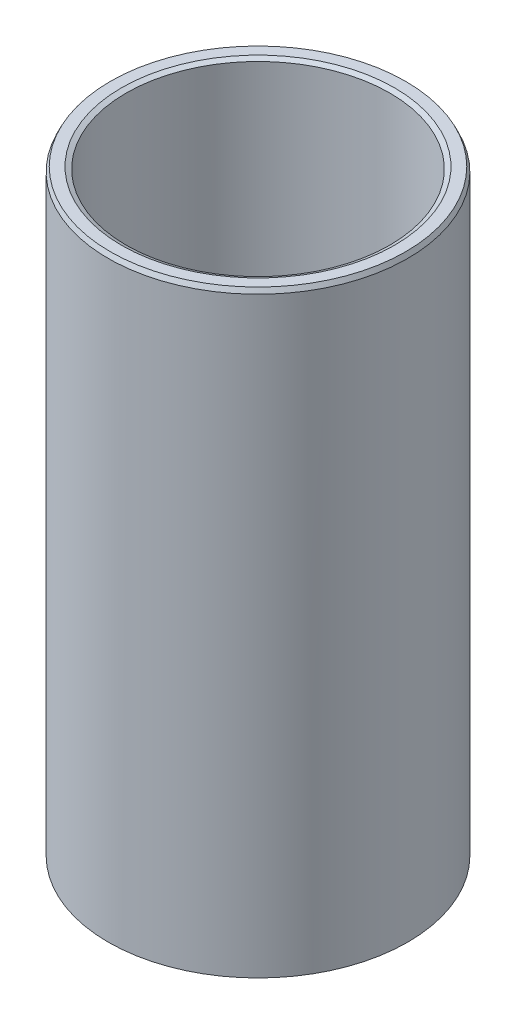
SolidWorks part; units mm, degrees
ref_plane "Front Plane" through (0, 0, 0) normal (0, 0, 1) x (1, 0, 0)
ref_plane "Top Plane" through (0, 0, 0) normal (0, 1, 0) x (1, 0, 0)
ref_plane "Right Plane" through (0, 0, 0) normal (1, 0, 0) x (0, 0, -1)
sketch "Sketch1" plane through (0, 0, 0) normal (0, 1, 0) x (1, 0, 0)
  circle A0 centre (0, 0) radius 60
  dimension "SLEEVE_OD" = 120
extrude "Boss-Extrude1" add sketch "Sketch1" along normal blind 239.8829
sketch "Sketch2" plane through (0, 0, 0) normal (0, 1, 0) x (1, 0, 0)
  circle A0 centre (0, 0) radius 52.7837
  dimension "BORE_D" = 105.5675
extrude "Cut-Extrude1" cut sketch "Sketch2" along normal through all
chamfer "Chamfer1" distance 1.8722 angle 25.181 4 edges at (0, 239.8829, 52.7837) (0, 0, 52.7837) (0, 0, 60) (0, 239.8829, 60) first distance on face at (0, 239.8829, 52.7837) first distance on face at (0, 0, 52.7837) first distance on face at (0, 239.8829, 60)
